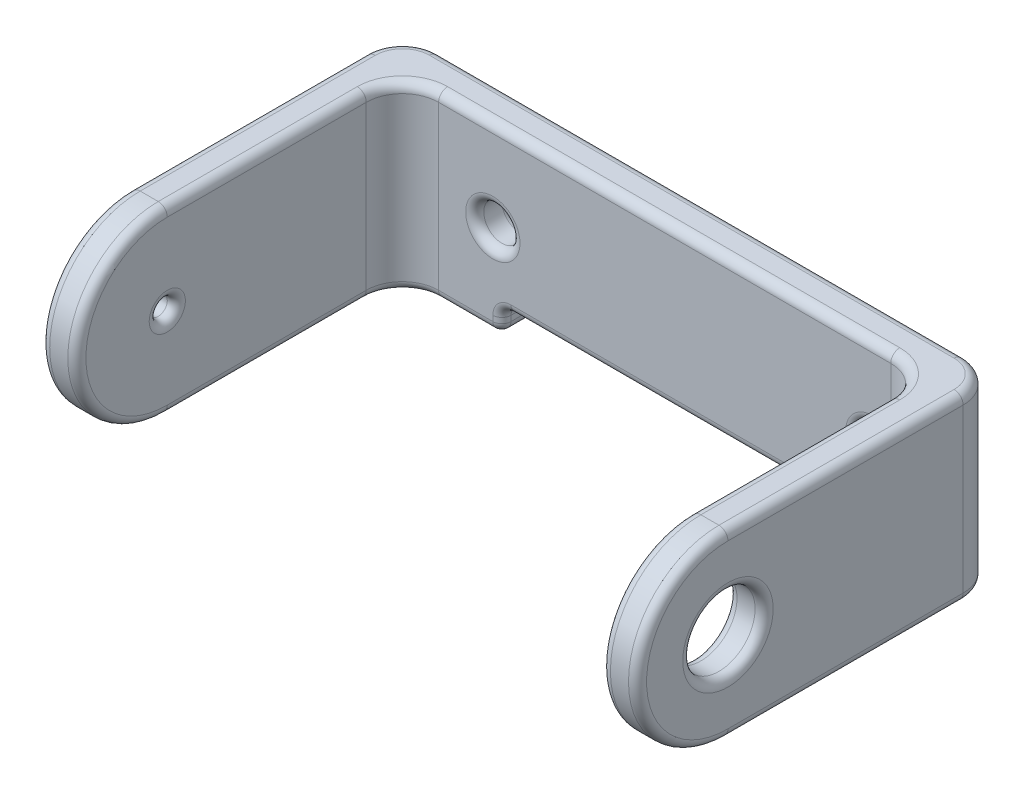
SolidWorks part; units mm, degrees
ref_plane "Plan de face" through (0, 0, 0) normal (0, 0, 1) x (1, 0, 0)
ref_plane "Plan de dessus" through (0, 0, 0) normal (0, 1, 0) x (1, 0, 0)
ref_plane "Plan de droite" through (0, 0, 0) normal (1, 0, 0) x (0, 0, -1)
sketch "Esquisse1" plane through (0, 0, 0) normal (0, 0, 1) x (1, 0, 0)
  line L0 (-14.5, 5) -> (-14.5, -5)
  line L1 (16.5, -5) -> (11, -5)
  line L2 (16.5, -5) -> (16.5, 5)
  line L3 (16.5, 5) -> (-16.5, 5)
  line L4 (-16.5, -5) -> (-16.5, 5)
  line L5 (16.5, -5) -> (-16.5, 5) construction
  line L6 (16.5, 5) -> (-16.5, -5) construction
  line L7 (14.5, 5) -> (14.5, -5)
  line L8 (-9, -5) -> (-16.5, -5)
  line L10 (-9, -5) -> (-9, -3.7)
  line L11 (-9, -3.7) -> (11, -3.7)
  line L12 (11, -5) -> (11, -3.7)
  line L13 (-16.5, -5) -> (-18.5, -5)
  line L14 (-16.5, -5) -> (-16.5, 5)
  line L15 (-16.5, 5) -> (-18.5, 5)
  point P0 (0, 0)
  dimension "D1" = 33
  dimension "D2" = 10
  dimension "D3" = 2
  dimension "D4" = 2
  dimension "D6" = 7.5
  dimension "D7" = 5.5
  dimension "D8" = 1.3
extrude "Boss.-Extru.1" add sketch "Esquisse1" along normal blind 20 contours L3 L7 L1 L2 | L4 L1 L0 L3 region at (-15.5, 0, 0) region at (15.5, 0, 0)
extrude "Boss.-Extru.3" add sketch "Esquisse1<4>" along normal blind 2 contours L7 L3 L0 L1 region at (-0.0985, 0.4284, 0)
sketch "Esquisse1<4>" plane through (0, 0, 0) normal (0, 0, 1) x (1, 0, 0) same geometry as "Esquisse1"
sketch "Esquisse2" plane through (-16.5, 0, 0) normal (-1, 0, 0) x (0, 0, 1)
  line L0 (20, -5) -> (0, -5) construction
  line L1 (20, 5) -> (10, 5)
  line L2 (20, 5) -> (20, -5)
  line L3 (20, -5) -> (10, -5)
  line L4 (10, 5) -> (10, -5)
  line L5 (10, 0) -> (20, 0)
  circle A0 centre (15, 0) radius 5
  circle A1 centre (15, 0) radius 0.5
  circle A2 centre (15, 0) radius 0.5
  line M3 (20, -5) -> (20, 5)
  line M4 (20, 5) -> (0, 5)
  dimension "D1" = 1
  dimension "D2" = 5
extrude "Enlèv. mat.-Extru.2" cut sketch "Esquisse2" against normal blind 50 contours A0 M3 M4 | A0 L3 M3 region at (-16.5, 3.8832, 18.8832) region at (-16.5, -3.8832, 18.8832)
fillet "Congé1" radius 2 1 edges at (-16.5, 0, 0)
extrude "Enlèv. mat.-Extru.4" cut sketch "Esquisse2<4>" against normal blind 10 contours L5 A1 | L5 A1 region at (-16.5, -0.2122, 15) region at (-16.5, 0.2122, 15)
sketch "Esquisse2<4>" plane through (-16.5, 0, 0) normal (-1, 0, 0) x (0, 0, 1) same geometry as "Esquisse2"
fillet "Congé2" radius 2 3 edges at (16.5, 0, 0)
sketch "Esquisse3" plane through (0, 0, 0) normal (0, 0, -1) x (-1, 0, 0)
  line L0 (14.5, 0) -> (-14.5, 0)
  line L1 (14.5, -5) -> (14.5, 5) construction
  line L2 (-14.5, 5) -> (-14.5, -5) construction
  circle A0 centre (9.5, 0) radius 1
  circle A1 centre (-11.5, 0) radius 1
  dimension "D1" = 2
  dimension "D2" = 2
  dimension "D3" = 3
  dimension "D4" = 5
extrude "Enlèv. mat.-Extru.3" cut sketch "Esquisse3" against normal blind 10 contours L0 A0 | L0 A0 | L0 A1 | L0 A1 region at (-9.5, -0.4244, 0) region at (-9.5, 0.4244, 0) region at (11.5, -0.4244, 0) region at (11.5, 0.4244, 0)
fillet "Congé3" radius 0.5 42 edges at (-16.5, 0, 20) (-16.5, 5, 8.5) (-15.9142, 5, 0.5858) (0, 5, 0) (15.9142, 5, 0.5858) (12.75, -5, 0) (-11.75, -5, 0) (15.9142, -5, 0.5858) (13.9142, -5, 2.5858) (16.5, 5, 8.5) (16.5, -5, 8.5) (16.5, 0, 20) (14.5, 0, 20) (13.9142, 5, 2.5858) (-14.5, 0, 20) (-13.9142, 5, 2.5858) (10.5, 0, 0) (12.5, 0, 2) (-10.5, 0, 0) (-8.5, 0, 2) (-15.9142, -5, 0.5858) (-16.5, -5, 8.5) (-13.9142, -5, 2.5858) (11, -4.35, 2) (11, -3.7, 1) (11, -5, 1) (11, -4.35, 0) (-9, -5, 1) (-9, -4.35, 0) (-9, -4.35, 2) (-9, -3.7, 1) (1, -3.7, 2) (1, -3.7, 0) (-14.5, 0.5, 15) (-16.5, 0, 15.5)
sketch "Esquisse5" plane through (16.5, 0, 0) normal (1, 0, 0) x (0, 0, -1)
  line L0 (-15, -4.5) -> (-15, 4.5)
  circle A0 centre (-15, 0) radius 2
  dimension "D1" = 4
extrude "Enlèv. mat.-Extru.5" cut sketch "Esquisse5" against normal blind 10 contours L0 A0 | L0 A0 region at (16.5, 0, 15.8488) region at (16.5, 0, 14.1512)
fillet "Congé4" radius 0.5 2 edges at (14.5, 2, 15) (16.5, 0, 13)
